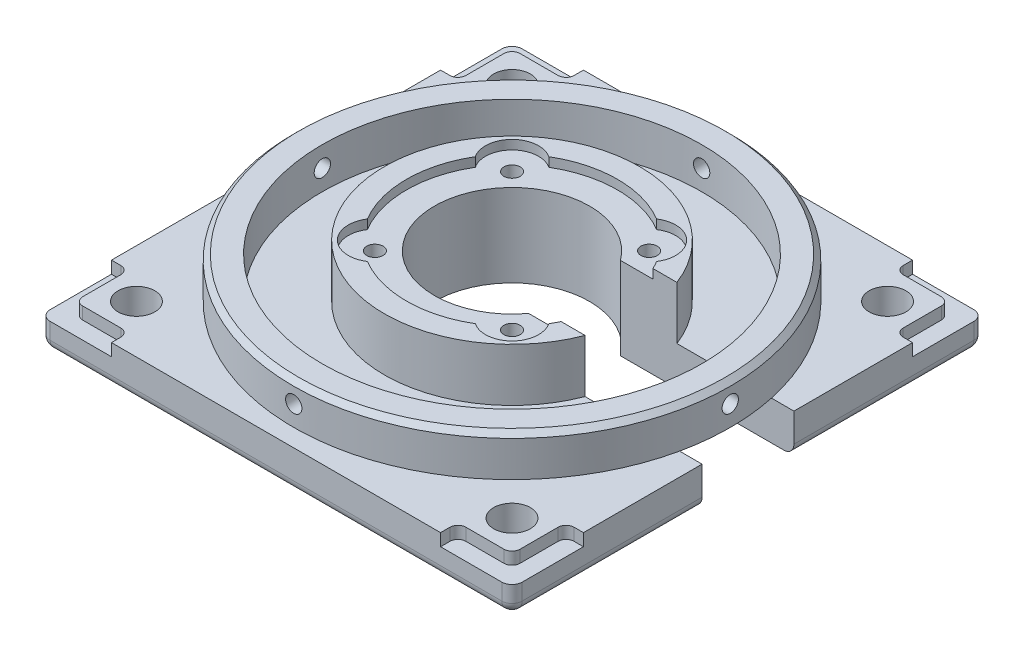
SolidWorks part; units mm, degrees
ref_plane "Front Plane" through (0, 0, 0) normal (0, 0, 1) x (1, 0, 0)
ref_plane "Top Plane" through (0, 0, 0) normal (0, 1, 0) x (1, 0, 0)
ref_plane "Right Plane" through (0, 0, 0) normal (1, 0, 0) x (0, 0, -1)
sketch "Sketch3" plane through (0, 0, 0) normal (0, 1, 0) x (1, 0, 0)
  circle A0 centre (0, 0) radius 7.6
  circle A1 centre (0, 0) radius 12.5
  dimension "D1" = 15.2
  dimension "D2" = 25
extrude "Boss-Extrude2" add sketch "Sketch3" along normal blind 9
sketch "Sketch4" plane through (0, 9, 0) normal (0, 1, 0) x (1, 0, 0)
  line L0 (6.1245, 4.5) -> (6.1245, -4.5)
  line L1 (6.1245, -4.5) -> (13.2817, -4.5)
  line L2 (13.2817, -4.5) -> (13.2817, 4.5)
  line L3 (13.2817, 4.5) -> (6.1245, 4.5)
  circle A0 centre (0, 0) radius 7.6 construction
  point P0 (0, 0)
  point P1 (6.1245, 4.5)
  point P3 (6.1245, -4.5)
  dimension "D1" = 4.5
extrude "Cut-Extrude2" cut sketch "Sketch4" against normal blind 9
sketch "Sketch5" plane through (0, 9, 0) normal (0, 1, 0) x (1, 0, 0)
  line L0 (0, 0) -> (17.4279, 0) construction
  line L1 (0, 0) -> (-11.2462, -11.2462) construction
  line L2 (0, 0) -> (-11.0539, 11.0539) construction
  point P0 (0, 0)
  point P1 (-6.715, 6.72)
  point P3 (-6.715, -6.72)
  point P9 (6.72, -6.715)
  point P10 (6.72, 6.715)
  dimension "D1" = 6.72
  dimension "D2" = 9.5
  dimension "D3" = 6.72
  dimension "D4" = 9.5
sketch "Sketch6" plane through (0, 9, 0) normal (0, 1, 0) x (1, 0, 0)
  line L0 (0, 0) -> (-11.2462, -11.2462) construction
  line L1 (0, 0) -> (-11.0539, 11.0539) construction
  line L2 (0, 0) -> (17.4279, 0) construction
  point P0 (5.2883, -8.8853)
  point P9 (-8.8853, 5.2883)
  point P12 (5.2883, 8.8853)
  point P14 (8.8893, -5.2817)
  point P15 (-5.2817, 8.8893)
  point P16 (8.8893, 5.2817)
  point P17 (-5.2817, -8.8893)
  point P18 (-8.8853, -5.2883)
  dimension "D1" = 2.6
  dimension "D2" = 10.34
  dimension "D3" = 2.6
  dimension "D4" = 10.34
sketch "Sketch8" plane through (0, 9, 0) normal (0, 1, 0) x (1, 0, 0)
  circle A0 centre (0, 0) radius 10.34
extrude "Cut-Extrude5" cut sketch "Sketch8" against normal blind 0.9
hole_wizard "Tap Drill for M2x0.4 Tap1" positions "3DSketch1" profile "Sketch10" hole size "M2x0.4" standard "ANSI Metric" end condition through all
sketch3d "3DSketch1"
  point P0 (6.72, 9, 6.715)
  point P3 (-6.715, 9, 6.72)
  point P6 (-6.715, 9, -6.72)
  point P9 (6.72, 9, -6.715)
sketch "Sketch10" plane through (6.72, 9, 6.715) normal (1, 0, 0) x (0, 0, 1)
  line L0 (0, 0) -> (0, 9)
  line L1 (0, 9) -> (0.8, 9)
  line L2 (0.8, 9) -> (0.8, 0)
  line L5 (0.8, 0) -> (0, 0)
  line L11 (0, -6.35) -> (0, 107.95) construction
  dimension "Thru Hole Dia." = 1.6
  dimension "Thru Hole Depth" = 9
sketch "Sketch11" plane through (0, 9, 0) normal (0, 1, 0) x (1, 0, 0)
  line L0 (8.8893, 5.2817) -> (5.2883, 8.8853)
  line L1 (8.8893, -5.2817) -> (5.2883, -8.8853)
  line L2 (-5.2817, -8.8893) -> (-8.8853, -5.2883)
  line L3 (-5.2817, 8.8893) -> (-8.8853, 5.2883)
  arc A0 (5.2883, -8.8853) -> (8.8893, -5.2817) centre (6.72, -6.715) ccw
  arc A1 (9.3094, 4.5) -> (9.3094, -4.5) centre (0, 0) ccw construction
  arc A2 (8.8893, 5.2817) -> (5.2883, 8.8853) centre (6.72, 6.715) ccw
  arc A3 (-5.2817, 8.8893) -> (-8.8853, 5.2883) centre (-6.715, 6.72) ccw
  arc A4 (-8.8853, -5.2883) -> (-5.2817, -8.8893) centre (-6.715, -6.72) ccw
extrude "Cut-Extrude6" cut sketch "Sketch11" against normal blind 0.9
sketch "Sketch12" plane through (0, 0, 0) normal (0, -1, 0) x (1, 0, 0)
  line L0 (0, 0) -> (17.7684, 0) construction
  line L1 (0, 0) -> (0, 18.0241) construction
  line L2 (23.125, -23.125) -> (-23.125, -23.125)
  line L3 (-23.125, -23.125) -> (-23.125, 23.125)
  line L4 (-23.125, 23.125) -> (23.125, 23.125)
  line L9 (6.4622, 4) -> (23.125, 4)
  line L11 (23.125, -4.5) -> (6.1245, -4.5)
  line L13 (23.125, -23.125) -> (23.125, -4.5)
  line L14 (23.125, 23.125) -> (23.125, 4)
  arc A0 (6.1245, -4.5) -> (6.4622, 4) centre (0, 0) cw
  circle A1 centre (0, 0) radius 7.6 construction
  point P0 (23.125, -23.125)
  point P4 (23.125, 23.125)
  point P5 (-23.125, 23.125)
  point P7 (-23.125, -23.125)
  dimension "D1" = 23.125
  dimension "D2" = 23.125
extrude "Boss-Extrude4" add sketch "Sketch12" against normal blind 3.81
fillet "Fillet2" radius 1 2 edges at (-23.125, 0, 0) (0, 0, 23.125)
fillet "Fillet3" radius 1 2 edges at (-22.8321, 0.2929, 22.8321) (-23.125, 2.405, 23.125)
sketch "Sketch13" plane through (0, 0, 0) normal (0, -1, 0) x (1, 0, 0)
  line L0 (0, 0) -> (-25.0462, 0) construction
  line L1 (0, 0) -> (0, 26.5218) construction
  point P0 (18.3989, -18.3989)
  point P5 (18.3989, 18.3989)
  point P6 (-18.3989, -18.3989)
  point P7 (-18.3989, 18.3989)
  dimension "D1" = 18.3989
  dimension "D2" = 18.3989
hole_wizard "M3 Clearance Hole1" positions "3DSketch2" profile "Sketch14" hole size "M3" standard "ANSI Metric" end condition through all
sketch3d "3DSketch2"
  point P0 (18.3989, 0, 18.3989)
  point P3 (18.3989, 0, -18.3989)
  point P6 (-18.3989, 0, -18.3989)
  point P9 (-18.3989, 0, 18.3989)
sketch "Sketch14" plane through (18.3989, 0, 18.3989) normal (1, 0, 0) x (0, 0, -1)
  line L0 (0, 0) -> (0, 9)
  line L1 (0, 9) -> (1.8, 9)
  line L2 (1.8, 9) -> (1.8, 0)
  line L5 (1.8, 0) -> (0, 0)
  line L11 (0, -6.35) -> (0, 107.95) construction
  dimension "Thru Hole Dia." = 3.6
  dimension "Thru Hole Depth" = 9
fillet "Fillet4" radius 1 7 edges at (23.125, 2.405, 23.125) (23.125, 0.2929, 22.8321) (-23.125, 2.405, -23.125) (-22.8321, 0.2929, -23.125) (23.125, 0, 13.0625) (23.125, 0, -13.8125) (0.5, 0, -23.125)
fillet "Fillet5" radius 1 2 edges at (22.8321, 0.2929, -22.8321) (23.125, 2.405, -23.125)
sketch "Sketch15" plane through (0, 3.81, 0) normal (0, 1, 0) x (1, 0, 0)
  circle A0 centre (0, 0) radius 21.4
  circle A1 centre (0, 0) radius 18.6
  point P0 (0, 0)
  dimension "D1" = 42.8
  dimension "D2" = 2.8
extrude "Boss-Extrude6" add sketch "Sketch15" along normal blind 4
hole_wizard "Tap Drill for M2x0.4 Tap2" positions "3DSketch4" profile "Sketch25" hole size "M2x0.4" standard "ANSI Metric" end condition up to next
sketch3d "3DSketch4"
  point P0 (21.4, 5.81, 0)
  dimension "D1" = 2
sketch "Sketch25" plane through (21.4, 5.81, 0) normal (0, 1, 0) x (0, 0, -1)
  line L0 (0, 0) -> (0, 2.8)
  line L1 (0, 2.8) -> (0.8, 2.8)
  line L2 (0.8, 2.8) -> (0.8, 0)
  line L5 (0.8, 0) -> (0, 0)
  line L11 (0, -6.35) -> (0, 107.95) construction
  dimension "Thru Hole Dia." = 1.6
  dimension "Thru Hole Depth" = 2.8
ref_axis "Axis1" through (0, 8.1, 0) along (0, -1, 0)
pattern_circular "CirPattern1" count 4 over 360 about axis through (0, 8.1, 0) along (0, -1, 0) of "Tap Drill for M2x0.4 Tap2"
chamfer "Chamfer1" distance 0.5 angle 45 1 edges at (0, 7.81, 21.4)
sketch "Sketch26" plane through (0, 3.81, 0) normal (0, 1, 0) x (1, 0, 0)
  line L1 (6.1245, -4.5) -> (23.125, -4.5)
  line L2 (6.1245, -4.5) -> (6.1245, 4.5)
  line L3 (6.1245, 4.5) -> (23.125, 4.5)
  line L4 (23.125, -4.5) -> (23.125, 4.5)
extrude "Cut-Extrude7" cut sketch "Sketch26" against normal up to next
sketch "Sketch27" plane through (0, 3.81, 0) normal (0, 1, 0) x (1, 0, 0)
  line L5 (22.125, -23.125) -> (-22.125, -23.125) construction
  line L6 (16.125, -23.125) -> (23.125, -23.125)
  line L11 (16.125, -23.125) -> (16.125, -21.425)
  line L12 (16.125, -21.425) -> (21.425, -21.425)
  line L13 (23.125, -23.125) -> (23.125, -21.425)
  line L14 (23.125, -4.5) -> (23.125, -22.125) construction
  line L16 (23.125, -23.125) -> (21.425, -23.125)
  line L17 (23.125, -23.125) -> (23.125, -16.125)
  line L18 (23.125, -16.125) -> (21.425, -16.125)
  line L19 (21.425, -21.425) -> (21.425, -16.125)
  line M18 (-22.125, -23.125) -> (22.125, -23.125)
  arc M19 (22.125, -23.125) -> (23.125, -22.125) centre (22.125, -22.125) ccw
  line M20 (23.125, -22.125) -> (23.125, -4.5)
extrude "Cut-Extrude9" cut sketch "Sketch27" against normal blind 1.2 contours L19 L12 L11 L6 L18 M18 M19 M20 region at (16.224, 3.81, 22.275)
fillet "Fillet6" radius 0.787 3 edges at (21.425, 3.21, 16.125) (21.425, 3.21, 21.425) (16.125, 3.21, 21.425)
pattern_circular "CirPattern4" count 4 over 360 about axis through (0, 8.1, 0) along (0, -1, 0) of "Cut-Extrude9", "Fillet6"
